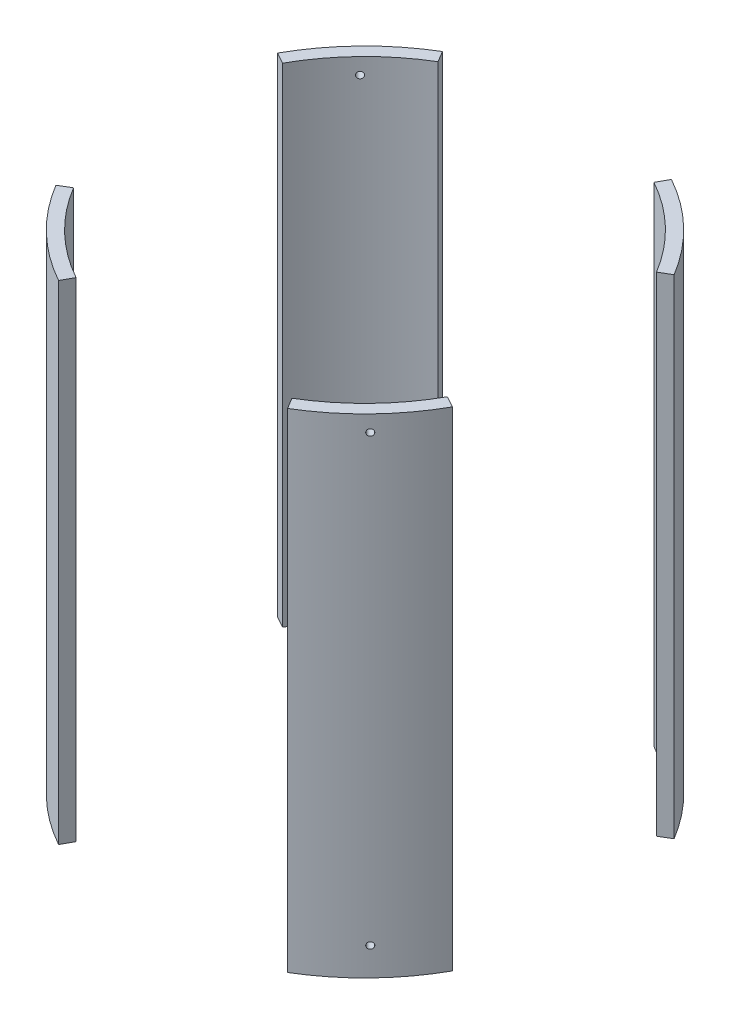
SolidWorks part; units mm, degrees
material "6061-T6 (SS)"
ref_plane "Front Plane" through (0, 0, 0) normal (0, 0, 1) x (1, 0, 0)
ref_plane "Top Plane" through (0, 0, 0) normal (0, 1, 0) x (1, 0, 0)
ref_plane "Right Plane" through (0, 0, 0) normal (1, 0, 0) x (0, 0, -1)
sketch "Sketch2" plane through (0, 0, 0) normal (0, 1, 0) x (1, 0, 0)
  circle A0 centre (0, 0) radius 88.9
  circle A1 centre (0, 0) radius 83.82
  dimension "D1" = 177.8
  dimension "D2" = 167.64
extrude "Boss-Extrude1" add sketch "Sketch2" along normal mid plane 192.7327
sketch "Sketch3" plane through (0, 0, 0) normal (0, 1, 0) x (1, 0, 0)
  line L0 (0, 0) -> (169.6618, 101.6776)
  line L1 (-58.1167, 96.9749) -> (0, 0)
  line L2 (0, 0) -> (53.9, 96.9749)
  line L3 (53.9, 96.9749) -> (-58.1167, 96.9749)
  line L4 (0, 0) -> (70.9917, -118.4586)
  line L5 (70.9917, -118.4586) -> (-65.8409, -118.4586)
  line L6 (-65.8409, -118.4586) -> (0, 0)
  line L7 (169.6618, 101.6776) -> (169.6618, -94.3004)
  line L8 (169.6618, -94.3004) -> (0, 0)
  line L9 (0, 0) -> (-123.7413, 68.7771)
  line L10 (-123.7413, 68.7771) -> (-123.7413, -74.1577)
  line L11 (-123.7413, -74.1577) -> (0, 0)
  dimension "D1" = 60
  dimension "D2" = 60
  dimension "D3" = 60
  dimension "D4" = 60
  dimension "D5" = 30
  dimension "D6" = 30
extrude "Cut-Extrude1" cut sketch "Sketch3" against normal through all both and the other way through all contours L8 L7 L0 | L2 L3 L1 | L10 L11 L9 | L6 L5 L4 region at (-1.4056, 0, -64.65) region at (1.7169, 0, 78.9724) region at (113.1078, 0, -2.4591) region at (-82.4942, 0, 1.7935)
ref_plane "Bolt reference plane" through (-56.3092, 0, 58.1758) normal (0.6955, 0, -0.7185) x (-0.7185, 0, -0.6955)
sketch "Sketch5" plane through (-56.3092, 0, 58.1758) normal (0.6955, 0, -0.7185) x (-0.7185, 0, -0.6955)
  line L0 (-23.009, -96.3663) -> (23.009, -96.3663) construction
  circle A0 centre (-0.0228, 90.0163) radius 1.27
  circle A1 centre (-0.0228, -85.2538) radius 1.27
  dimension "D1" = 2.54
  dimension "D4" = 11.1125
  dimension "D2" = 21.717
  dimension "D3" = 6.35
extrude "Bolt holes" cut sketch "Sketch5" against normal through all
pattern_circular "Bolt pattern" count 4 over 360 about axis through (0, 96.3663, 0) along (0, 1, 0) of "Bolt holes"
equation "\"D1@Boss-Extrude1\"=3*12"
